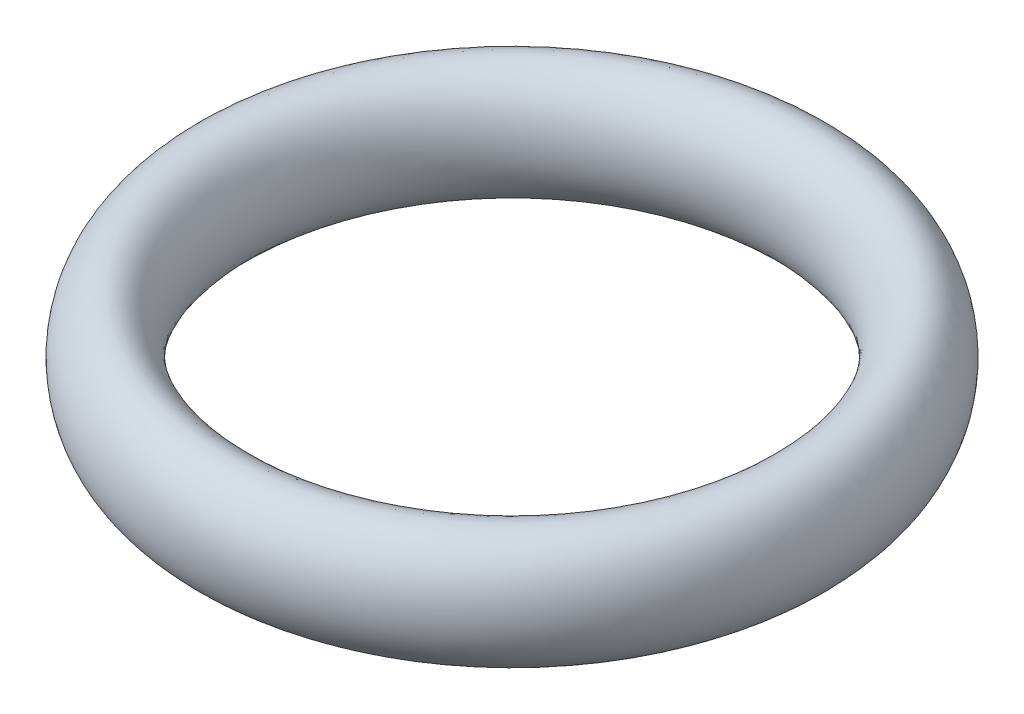
SolidWorks part; units mm, degrees
note: '?' marks a value the reader was unsure of.
material "PW20:30:Sc:0:"
ref_plane "Plane1" through (0, 0, 0) normal (0, 0, 1) x (1, 0, 0)
ref_plane "Plane2" through (0, 0, 0) normal (0, 1, 0) x (1, 0, 0)
ref_plane "Plane3" through (0, 0, 0) normal (1, 0, 0) x (0, 0, -1)
sketch "Sketch1" plane through (0, 0, 0) normal (0, 0, 1) x (1, 0, 0)
  line L0 (0, 0) -> (0, 1.778) construction
  line L1 (4.3561, 1.778) -> (4.3561, 0) construction
  ellipse E0 centre (4.3561, 0.889) end of major axis (4.3561, 1.778) minor radius 0.635
  dimension "D1" = 1.778
  dimension "D2" = 1.27
  dimension "D3" = 3.7211
revolve "Body" add sketch "Sketch1" angle 360 about L0
ref_axis "Axis1" through (0, -50, 0) along (0, 1, 0)?
